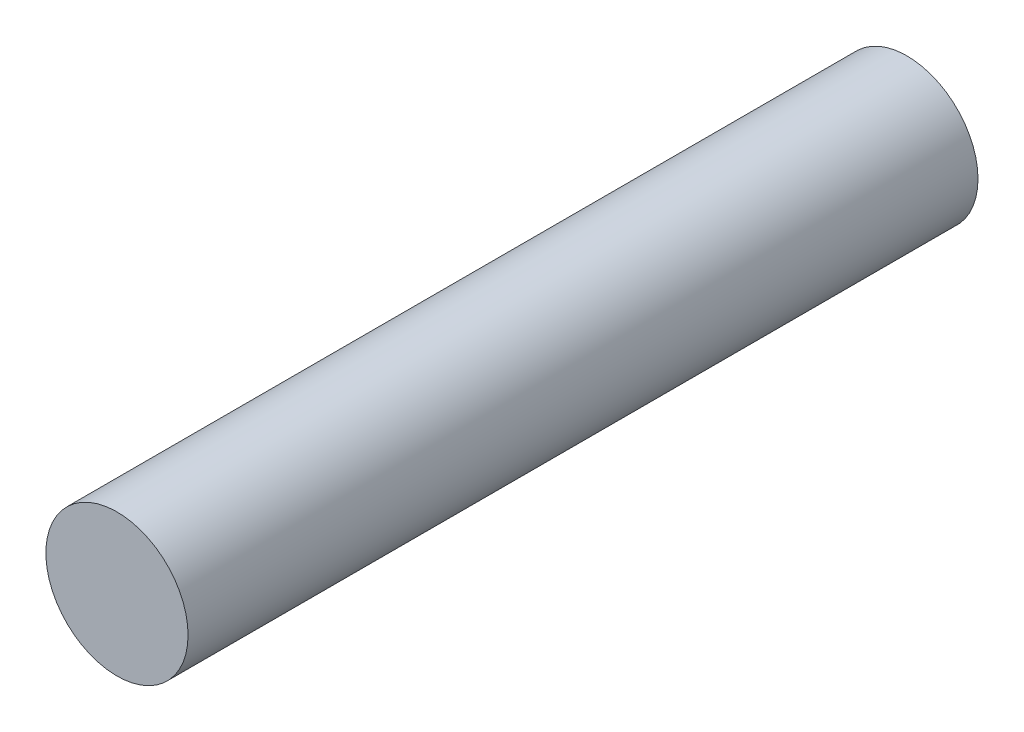
SolidWorks part; units mm, degrees
ref_plane "Plan de face" through (0, 0, 0) normal (0, 0, 1) x (1, 0, 0)
ref_plane "Plan de dessus" through (0, 0, 0) normal (0, 1, 0) x (1, 0, 0)
ref_plane "Plan de droite" through (0, 0, 0) normal (1, 0, 0) x (0, 0, -1)
sketch "Esquisse1" plane through (0, 0, 0) normal (0, 0, 1) x (1, 0, 0)
  circle A0 centre (0, 0) radius 4.5
  dimension "D1" = 9
extrude "Boss.-Extru.1" add sketch "Esquisse1" along normal blind 50
